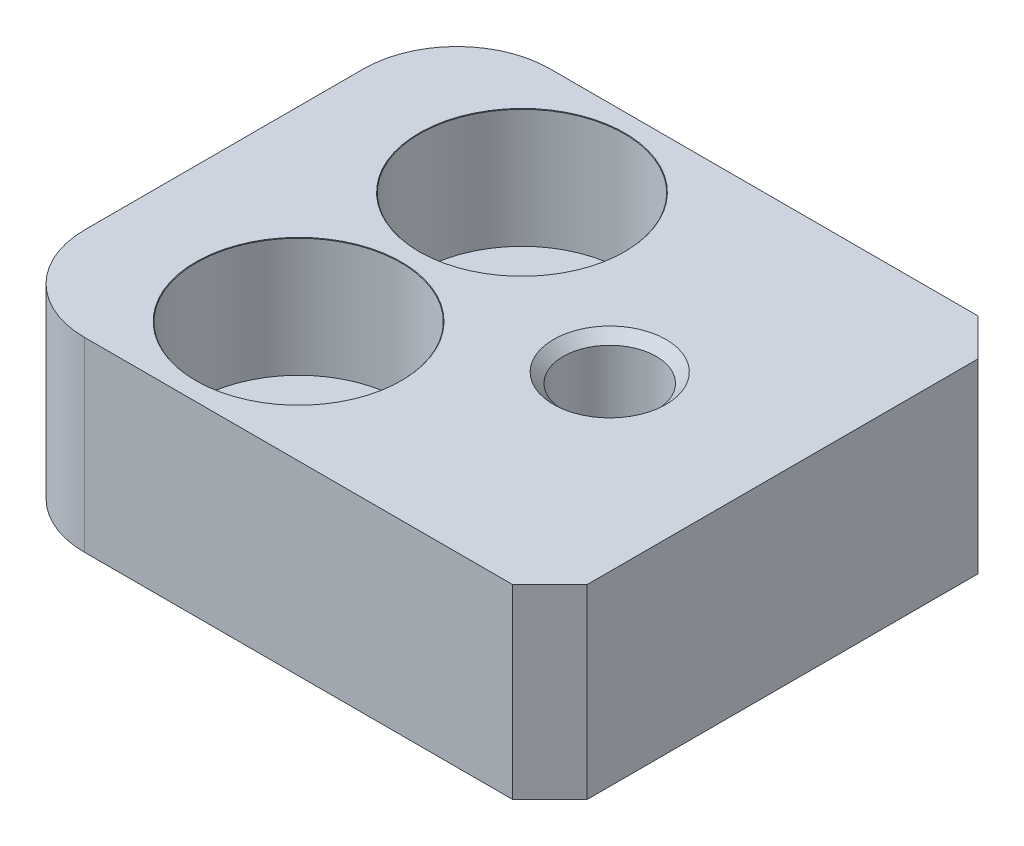
SolidWorks part; units mm, degrees
material "Plain Carbon Steel"
ref_plane "Front Plane" through (0, 0, 0) normal (0, 0, 1) x (1, 0, 0)
ref_plane "Top Plane" through (0, 0, 0) normal (0, 1, 0) x (1, 0, 0)
ref_plane "Right Plane" through (0, 0, 0) normal (1, 0, 0) x (0, 0, -1)
sketch "Sketch1" plane through (0, 0, 0) normal (0, 1, 0) x (1, 0, 0)
  line L0 (-15, 0) -> (15, 0) construction
  line L1 (-15, -12.5) -> (15, -12.5)
  line L2 (-15, -12.5) -> (-15, 12.5)
  line L3 (-15, 12.5) -> (15, 12.5)
  line L4 (15, -12.5) -> (15, 12.5)
  line L5 (0, -12.5) -> (0, 12.5) construction
  dimension "D1" = 30
  dimension "D2" = 25
extrude "Boss-Extrude1" add sketch "Sketch1" along normal blind 10
fillet "Fillet1" radius 5 2 edges at (-15, 5, -12.5) (-15, 5, 12.5)
sketch "Sketch2" plane through (0, 10, 0) normal (0, 1, 0) x (1, 0, 0)
  line L0 (-15, 0) -> (15, 0) construction
  line L1 (-15, 7.5) -> (-15, -7.5) construction
  line L2 (15, -12.5) -> (15, 12.5) construction
  point P0 (-5, 6)
  point P2 (-5, -6)
  dimension "D1" = 12
  dimension "D2" = 10
hole_wizard "CBORE for M6 Hex Socket Head Cap Screw1" positions "Sketch2" profile "Sketch3" counterbore size "M6" standard "ISO" end condition through all
sketch "Sketch3" plane through (-5, 10, -6) normal (1, 0, 0) x (0, 0, 1)
  line L0 (0, 0) -> (0, 10)
  line L1 (3.3, 9.975) -> (3.325, 10)
  line L2 (5.5, 6.4) -> (3.3, 6.4)
  line L3 (3.3, 6.4) -> (3.3, 9.975)
  line L5 (5.5, 6.4) -> (5.5, 0.025)
  line L6 (5.5, 0.025) -> (5.525, 0)
  line L7 (5.525, 0) -> (0, 0)
  line L8 (-5.5, 0.025) -> (-5.525, 0) construction
  line L11 (0, -6.35) -> (0, 107.95) construction
  line L12 (3.325, 10) -> (0, 10)
  line L13 (-3.3, 9.975) -> (-3.325, 10) construction
  dimension "Thru Hole Dia." = 6.6
  dimension "Thru Hole Depth" = 10
  dimension "C'Bore Dia." = 11
  dimension "C'Bore Depth" = 6.4
  dimension "Near C'Sink Dia." = 11.05
  dimension "Near C'Sink Angle" = 90
  dimension "Far C'Sink Dia." = 6.65
  dimension "Far C'Sink Angle" = 90
sketch "Sketch4" plane through (0, 0, 0) normal (0, -1, 0) x (-1, 0, 0)
  line L0 (15, 7.5) -> (15, -7.5) construction
  point P0 (-5.7152, 0)
  dimension "D1" = 20.7152
hole_wizard "M6 Tapped Hole1" positions "Sketch4" profile "Sketch5" tap size "M6" standard "ISO" end condition through all
sketch "Sketch5" plane through (5.7152, 0, 0) normal (1, 0, 0) x (0, 0, -1)
  line L0 (0, 0) -> (0, 10)
  line L1 (0, 10) -> (3.025, 10)
  line L2 (2.5, 9.475) -> (2.5, 0.525)
  line L3 (2.5, 0.525) -> (3.025, 0)
  line L5 (3.025, 0) -> (0, 0)
  line L6 (-2.5, 0.525) -> (-3.025, 0) construction
  line L7 (3.025, 10) -> (2.5, 9.475)
  line L8 (-3.025, 10) -> (-2.5, 9.475) construction
  line L11 (0, -6.35) -> (0, 107.95) construction
  dimension "Thru Tap Drill Dia." = 5
  dimension "Thru Tap Drill Depth" = 10
  dimension "Near C'Sink Dia." = 6.05
  dimension "Near C'Sink Angle" = 90
  dimension "Far C'Sink Dia." = 6.05
  dimension "Far C'Sink Angle" = 90
cosmetic thread "Hole Thread1" parameters "D2"=6
chamfer "Chamfer1" distance 2 angle 45 2 edges at (15, 5, -12.5) (15, 5, 12.5)
